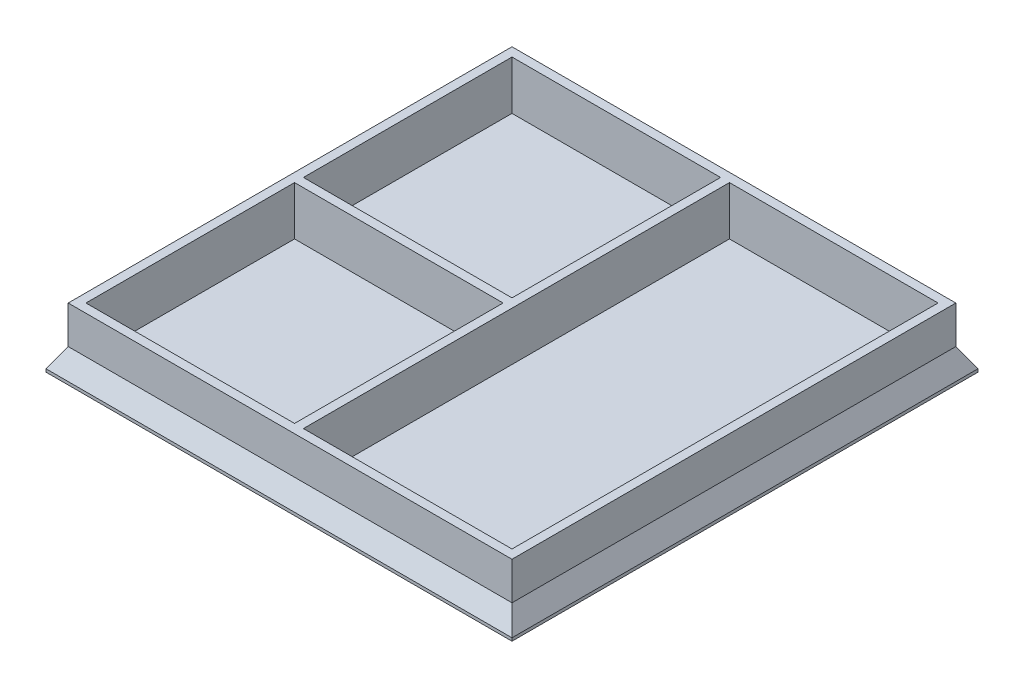
SolidWorks part; units mm, degrees
ref_plane "Přední rovina" through (0, 0, 0) normal (0, 0, 1) x (1, 0, 0)
ref_plane "Horní rovina" through (0, 0, 0) normal (0, 1, 0) x (1, 0, 0)
ref_plane "Pravá rovina" through (0, 0, 0) normal (1, 0, 0) x (0, 0, -1)
sketch "Skica1" plane through (0, 0, 0) normal (0, 1, 0) x (1, 0, 0)
  line L0 (-84, 84) -> (0, 0) construction
  line L1 (0, 0) -> (-84, 0)
  line L2 (0, 0) -> (0, 84)
  line L3 (0, 84) -> (-84, 84)
  line L4 (-84, 0) -> (-84, 84)
  line L5 (-84, 0) -> (0, 84) construction
  line L6 (-42, 82) -> (-42, 2) construction
  line L7 (-82, 82) -> (-2, 82)
  line L8 (-82, 82) -> (-82, 2)
  line L9 (-82, 2) -> (-2, 2)
  line L10 (-2, 82) -> (-2, 2)
  line L11 (-82, 82) -> (-2, 2) construction
  line L12 (-82, 2) -> (-2, 82) construction
  line L13 (-82, 42) -> (-2, 42) construction
  line L15 (-41.2, 80.4) -> (-3.6, 80.4)
  line L16 (-41.2, 80.4) -> (-41.2, 3.6)
  line L17 (-41.2, 3.6) -> (-3.6, 3.6)
  line L18 (-3.6, 80.4) -> (-3.6, 3.6)
  line L19 (-80.4, 80.4) -> (-42.8, 80.4)
  line L20 (-80.4, 80.4) -> (-80.4, 42.8)
  line L21 (-80.4, 42.8) -> (-42.8, 42.8)
  line L22 (-42.8, 80.4) -> (-42.8, 42.8)
  line L23 (-80.4, 41.2) -> (-42.8, 41.2)
  line L24 (-80.4, 41.2) -> (-80.4, 3.6)
  line L25 (-80.4, 3.6) -> (-42.8, 3.6)
  line L26 (-42.8, 41.2) -> (-42.8, 3.6)
  point P4 (-42, 42)
  dimension "D1" = 84
  dimension "D2" = 84
  dimension "D3" = 80
  dimension "D4" = 80
  dimension "D5" = 1.6
  dimension "D6" = 1.6
  dimension "D7" = 0.8
  dimension "D8" = 1.6
  dimension "D9" = 1.6
  dimension "D10" = 1.6
  dimension "D11" = 0.8
  dimension "D12" = 0.8
  dimension "D13" = 1.6
  dimension "D14" = 0.8
  dimension "D15" = 1.6
  dimension "D16" = 0.8
extrude "Přidat vysunutím1" add sketch "Skica1" along normal blind 2 contours L3 L4 L1 L2
extrude "Přidat vysunutím2" add sketch "Skica1<3>" along normal blind 10.8 contours L10 L7 L8 L9 L15 L18 L17 L16 L19 L22 L21 L20 L23 L26 L25 L24 region at (-43.7219, 0, -42)
sketch "Skica1<3>" plane through (0, 0, 0) normal (0, 1, 0) x (1, 0, 0) same geometry as "Skica1"
extrude "Přidat vysunutím3" add sketch "Skica1<4>" along normal blind 4 contours L4 L1 L2 L3 L7 L10 L9 L8 region at (-42, 0, -1.1879)
sketch "Skica1<4>" plane through (0, 0, 0) normal (0, 1, 0) x (1, 0, 0) same geometry as "Skica1"
chamfer "Zkosení2" distance 2 angle 60 4 edges at (-84, 4, -42) (-42, 4, -84) (0, 4, -42) (-42, 4, 0) first distance on face at (-42, 4, -42)
